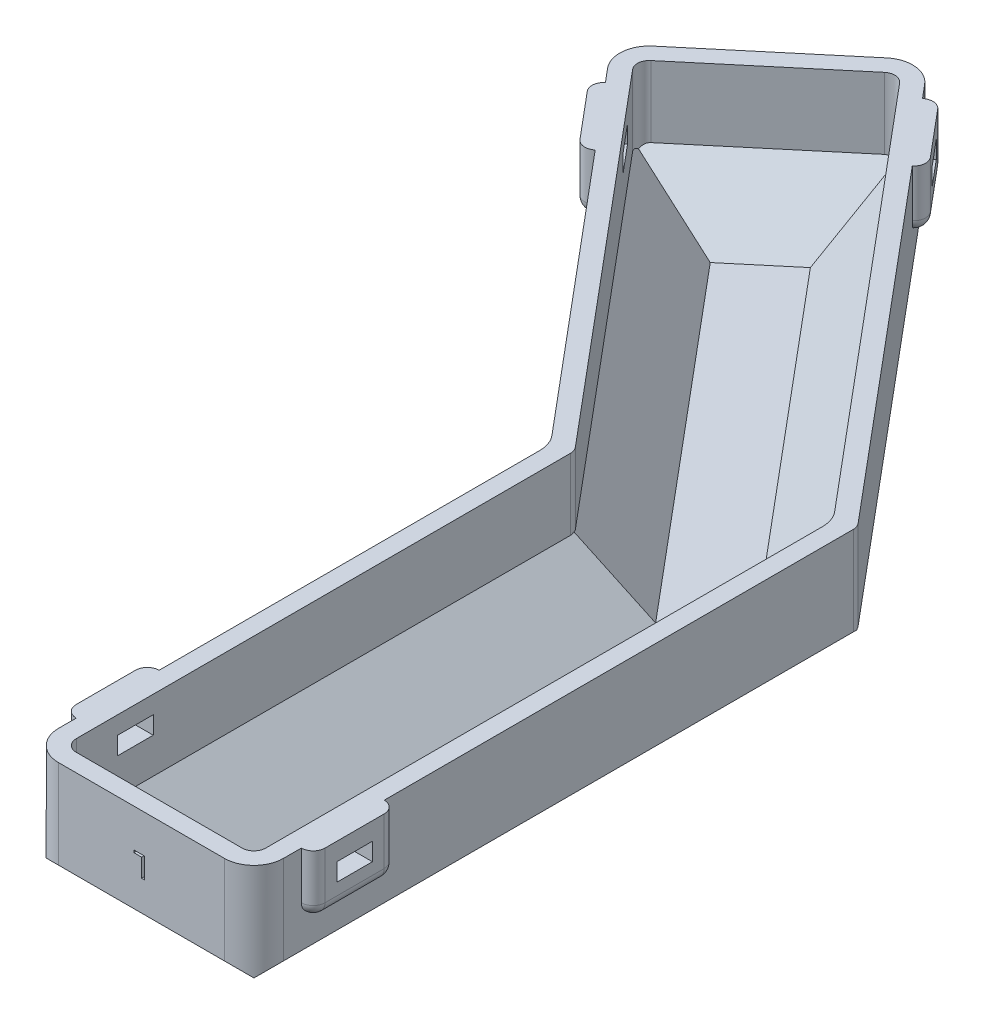
SolidWorks part; units mm, degrees
ref_plane "Front Plane" through (0, 0, 0) normal (0, 0, 1) x (1, 0, 0)
ref_plane "Top Plane" through (0, 0, 0) normal (0, 1, 0) x (1, 0, 0)
ref_plane "Right Plane" through (0, 0, 0) normal (1, 0, 0) x (0, 0, -1)
sketch "Sketch1" plane through (0, 0, 0) normal (0, 1, 0) x (1, 0, 0)
  line L0 (0, -95) -> (0, 0) construction
  line L1 (0, 0) -> (-57.8509, 68.944) construction
  line L2 (19, -95) -> (19, 6.9154)
  line L3 (-19, -95) -> (-19, -6.9154)
  line L4 (-19, -95) -> (19, -95)
  line L5 (19, 6.9154) -> (-43.296, 81.157)
  line L6 (-72.4057, 56.731) -> (-43.296, 81.157)
  line L7 (-72.4057, 56.731) -> (-19, -6.9154)
  line L8 (-68.1792, 56.3613) -> (-43.6658, 76.9305) construction
  line L9 (-68.1792, 56.3613) -> (-16, -5.8235) construction
  line L10 (-16, -5.8235) -> (-16, -92) construction
  line L11 (-16, -92) -> (16, -92) construction
  line L12 (16, -92) -> (16, 5.8235) construction
  line L13 (16, 5.8235) -> (-43.6658, 76.9305) construction
  point P9 (0, -95)
  point P10 (-57.8509, 68.944)
  point P12 (-55.9225, 66.6459)
  point P13 (0, -92)
  dimension "D1" = 95
  dimension "D2" = 90
  dimension "D3" = 38
  dimension "D4" = 38
  dimension "D5" = 140
  dimension "D6" = 32
  dimension "D7" = 32
  dimension "D8" = 3
  dimension "D9" = 3
extrude "Boss-Extrude1" add sketch "Sketch1" along normal blind 25
sketch "Sketch2" plane through (0, 25, 0) normal (0, 1, 0) x (1, 0, 0)
  line L0 (-68.1792, 56.3613) -> (-43.6658, 76.9305)
  line L1 (-68.1792, 56.3613) -> (-16, -5.8235)
  line L2 (-16, -5.8235) -> (-16, -92)
  line L3 (-16, -92) -> (16, -92)
  line L4 (16, -92) -> (16, 5.8235)
  line L5 (16, 5.8235) -> (-43.6658, 76.9305)
  line L6 (0, 0) -> (-57.8509, 68.944) construction
  line L7 (-43.296, 81.157) -> (-72.4057, 56.731) construction
  line L8 (0, 0) -> (0, -95) construction
  line L9 (-19, -95) -> (19, -95) construction
  point P0 (-55.9225, 66.6459)
  point P1 (0, -92)
  dimension "D1" = 32
  dimension "D2" = 32
  dimension "D3" = 3
  dimension "D4" = 3
extrude "Cut-Extrude1" cut sketch "Sketch2" against normal blind 22
chamfer "Chamfer1" distance 10 angle 45 12 edges at (-55.9225, 3, -66.6459) (-13.8329, 3, -41.377) (16, 3, 43.0882) (0, 3, 92) (-16, 3, 48.9118) (-42.0896, 3, -25.2689) (-45.7029, 0, -24.9078) (-57.8509, 0, -68.944) (-12.148, 0, -44.0362) (19, 0, 44.0423) (-19, 0, 50.9577) (0, 0, 95)
fillet "Fillet1" radius 2 6 edges at (-16, 19, 92) (16, 19, 92) (-16, 19, 5.8235) (19, 17.5, -6.9154) (-68.1792, 19, -56.3613) (-43.6658, 19, -76.9305)
fillet "Fillet2" radius 5 6 edges at (-19, 17.5, 95) (19, 17.5, 95) (-19, 17.5, 6.9154) (16, 19, -5.8235) (-43.296, 17.5, -81.157) (-72.4057, 17.5, -56.731)
sketch "Sketch3" plane through (-14.5548, 0, 12.213) normal (-0.766, 0, 0.6428) x (0.6428, 0, 0.766)
  line L0 (-85, 25) -> (-8.7353, 25) construction
  line L1 (-68, 15) -> (-82, 15)
  line L2 (-68, 15) -> (-68, 25)
  line L3 (-68, 25) -> (-82, 25)
  line L4 (-82, 15) -> (-82, 25)
  line L5 (-68, 15) -> (-82, 25) construction
  line L6 (-68, 25) -> (-82, 15) construction
  line L7 (-85, 25) -> (-85, 10) construction
  point P0 (-75, 20)
  dimension "D1" = 10
  dimension "D2" = 14
  dimension "D3" = 3
extrude "Boss-Extrude2" add sketch "Sketch3" along normal blind 2
sketch "Sketch4" plane through (14.5548, 0, -12.213) normal (0.766, 0, -0.6428) x (-0.6428, 0, -0.766)
  line L0 (-6.1875, 25) -> (85, 25) construction
  line L1 (82, 15) -> (68, 15)
  line L2 (82, 15) -> (82, 25)
  line L3 (82, 25) -> (68, 25)
  line L4 (68, 15) -> (68, 25)
  line L5 (82, 15) -> (68, 25) construction
  line L6 (82, 25) -> (68, 15) construction
  line L7 (85, 10) -> (85, 25) construction
  point P0 (75, 20)
  dimension "D1" = 3
  dimension "D2" = 10
  dimension "D3" = 14
extrude "Boss-Extrude3" add sketch "Sketch4" along normal blind 2
sketch "Sketch5" plane through (16.0869, 0, -13.4985) normal (0.766, 0, -0.6428) x (-0.6428, 0, -0.766)
  line L0 (82, 15) -> (82, 25) construction
  line L1 (78, 19) -> (72, 19)
  line L2 (78, 19) -> (78, 22)
  line L3 (78, 22) -> (72, 22)
  line L4 (72, 19) -> (72, 22)
  line L5 (78, 19) -> (72, 22) construction
  line L6 (78, 22) -> (72, 19) construction
  line L7 (82, 25) -> (68, 25) construction
  point P0 (75, 20.5)
  dimension "D1" = 4
  dimension "D2" = 3
  dimension "D3" = 3
  dimension "D4" = 6
extrude "Cut-Extrude2" cut sketch "Sketch5" against normal through all both and the other way through all
sketch "Sketch6" plane through (-19, 0, 0) normal (-1, 0, 0) x (0, 0, 1)
  line L0 (8.7353, 25) -> (90, 25) construction
  line L1 (87, 15) -> (73, 15)
  line L2 (87, 15) -> (87, 25)
  line L3 (87, 25) -> (73, 25)
  line L4 (73, 15) -> (73, 25)
  line L5 (87, 15) -> (73, 25) construction
  line L6 (87, 25) -> (73, 15) construction
  line L7 (90, 10) -> (90, 25) construction
  point P0 (80, 20)
  dimension "D1" = 3
  dimension "D2" = 14
  dimension "D3" = 10
extrude "Boss-Extrude4" add sketch "Sketch6" along normal blind 2
sketch "Sketch7" plane through (19, 0, 0) normal (1, 0, 0) x (0, 0, -1)
  line L0 (-90, 25) -> (6.1875, 25) construction
  line L1 (-73, 15) -> (-87, 15)
  line L2 (-73, 15) -> (-73, 25)
  line L3 (-73, 25) -> (-87, 25)
  line L4 (-87, 15) -> (-87, 25)
  line L5 (-73, 15) -> (-87, 25) construction
  line L6 (-73, 25) -> (-87, 15) construction
  line L7 (-90, 25) -> (-90, 10) construction
  point P0 (-80, 20)
  dimension "D1" = 10
  dimension "D2" = 14
  dimension "D3" = 3
extrude "Boss-Extrude5" add sketch "Sketch7" along normal blind 2
sketch "Sketch8" plane through (21, 0, 0) normal (1, 0, 0) x (0, 0, -1)
  line L0 (-73, 25) -> (-87, 25) construction
  line L1 (-77, 19) -> (-83, 19)
  line L2 (-77, 19) -> (-77, 22)
  line L3 (-77, 22) -> (-83, 22)
  line L4 (-83, 19) -> (-83, 22)
  line L5 (-77, 19) -> (-83, 22) construction
  line L6 (-77, 22) -> (-83, 19) construction
  line L7 (-73, 15) -> (-73, 25) construction
  point P0 (-80, 20.5)
  dimension "D1" = 6
  dimension "D2" = 3
  dimension "D3" = 3
  dimension "D4" = 4
extrude "Cut-Extrude3" cut sketch "Sketch8" against normal through all both and the other way through all
fillet "Fillet4" radius 2 12 edges at (-21, 20, 87) (-21, 15, 80) (-21, 20, 73) (-59.7965, 20, -38.5925) (-68.7955, 20, -49.3171) (-64.296, 15, -43.9548) (-36.6217, 20, -76.3142) (-27.6226, 20, -65.5896) (-32.1221, 15, -70.9519) (21, 20, 73) (21, 20, 87) (21, 15, 80)
sketch "Sketch9" plane through (0, 0, 95) normal (0, 0, 1) x (1, 0, 0)
  line L0 (0, 10) -> (0, 25) construction
  line L1 (-14, 10) -> (14, 10) construction
  line L2 (-14, 25) -> (14, 25) construction
  line L3 (14, 17.5) -> (-14, 17.5) construction
  line L4 (14, 10) -> (14, 25) construction
  line L5 (-14, 25) -> (-14, 10) construction
  text T0 "<b><r180>L</r></b>"
  point P7 (1.2189, 19.4499)
  point P8 (0, 0)
  point P9 (0, 0)
  point P16 (0, 0)
extrude "Cut-Extrude4" cut sketch "Sketch9" against normal blind 0.5
